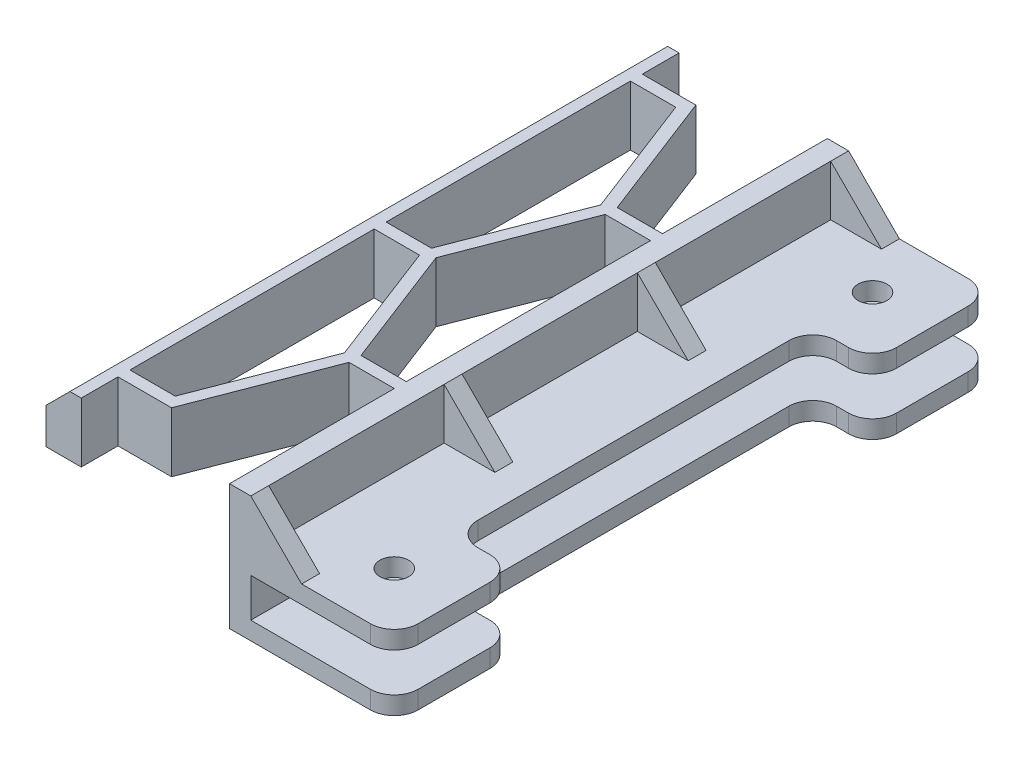
SolidWorks part; units mm, degrees
ref_plane "Front Plane" through (0, 0, 0) normal (0, 0, 1) x (1, 0, 0)
ref_plane "Top Plane" through (0, 0, 0) normal (0, 1, 0) x (1, 0, 0)
ref_plane "Right Plane" through (0, 0, 0) normal (1, 0, 0) x (0, 0, -1)
ref_plane "Plane1" through (0, 4, 0) normal (0, 1, 0) x (1, 0, 0)
ref_plane "Plane2" through (0, 3.25, 0) normal (0, 1, 0) x (1, 0, 0)
sketch "Sketch1" plane through (0, 4, 0) normal (0, 1, 0) x (1, 0, 0)
  line L0 (-14.18, 50) -> (-14.18, 46.9286)
  line L1 (-17.13, 50) -> (-14.18, 50)
  line L2 (-17.13, 50) -> (-17.13, 0)
  line L3 (-17.13, 0) -> (-14.18, 0)
  line L5 (-1.78, 50) -> (0, 50)
  line L7 (-1.78, 0) -> (0, 0)
  line L8 (0, 50) -> (0, 0)
  line L9 (-1.78, 50) -> (-1.78, 36.2143)
  line L18 (-14.18, 25) -> (-1.78, 25) construction
  line L20 (-14.18, 25) -> (-10.0467, 25) construction
  line L21 (-10.0467, 25) -> (-5.9133, 35.7143) construction
  line L22 (-5.9133, 35.7143) -> (-1.78, 35.7143) construction
  line L23 (-5.9133, 35.7143) -> (-10.0467, 46.4286) construction
  line L24 (-10.0467, 46.4286) -> (-14.18, 46.4286) construction
  line L25 (-10.0467, 3.5714) -> (-14.18, 3.5714) construction
  line L26 (-5.9133, 14.2857) -> (-10.0467, 3.5714) construction
  line L27 (-5.9133, 14.2857) -> (-1.78, 14.2857) construction
  line L28 (-10.0467, 25) -> (-5.9133, 14.2857) construction
  line L29 (-6.4492, 35.7143) -> (-10.3897, 45.9286)
  line L30 (-10.3897, 45.9286) -> (-14.18, 45.9286)
  line L31 (-5.5703, 36.2143) -> (-1.78, 36.2143)
  line L32 (-10.3897, 25.5) -> (-6.4492, 35.7143)
  line L33 (-14.18, 25.5) -> (-10.3897, 25.5)
  line L34 (-9.5108, 25) -> (-5.5703, 14.7857)
  line L35 (-5.5703, 14.7857) -> (-1.78, 14.7857)
  line L36 (-5.5703, 13.7857) -> (-9.7036, 3.0714)
  line L37 (-9.7036, 3.0714) -> (-14.18, 3.0714)
  line L38 (-5.5703, 36.2143) -> (-9.7036, 46.9286)
  line L39 (-9.7036, 46.9286) -> (-14.18, 46.9286)
  line L40 (-5.5703, 35.2143) -> (-1.78, 35.2143)
  line L41 (-9.5802, 24.82) -> (-5.5703, 35.2143)
  line L42 (-14.18, 24.5) -> (-10.3897, 24.5)
  line L43 (-10.3897, 24.5) -> (-6.4492, 14.2857)
  line L44 (-5.5703, 13.7857) -> (-1.78, 13.7857)
  line L45 (-6.4492, 14.2857) -> (-10.3897, 4.0714)
  line L46 (-10.3897, 4.0714) -> (-14.18, 4.0714)
  line L47 (-14.18, 45.9286) -> (-14.18, 25.5)
  line L48 (-14.18, 24.5) -> (-14.18, 4.0714)
  line L49 (-14.18, 3.0714) -> (-14.18, 0)
  line L50 (-1.78, 35.2143) -> (-1.78, 14.7857)
  line L51 (-1.78, 13.7857) -> (-1.78, 0)
  line L52 (-10.3897, 25.5) -> (-10.0467, 25.5) construction
  line L53 (-5.9133, 36.2143) -> (-5.5703, 36.2143) construction
  line L54 (-5.9133, 36.2143) -> (-1.78, 36.2143) construction
  line L55 (-5.4468, 35.8942) -> (-5.5703, 36.2143) construction
  line L56 (-5.4468, 35.8942) -> (-9.7036, 46.9286) construction
  line L57 (-5.5703, 35.2143) -> (-5.4468, 35.5343) construction
  line L58 (-9.5802, 24.82) -> (-5.4468, 35.5343) construction
  line L59 (-5.9133, 35.2143) -> (-5.5703, 35.2143) construction
  line L60 (-5.9133, 35.2143) -> (-1.78, 35.2143) construction
  line L61 (-6.3798, 35.5343) -> (-6.4492, 35.7143) construction
  line L62 (-6.3798, 35.5343) -> (-10.3897, 45.9286) construction
  line L63 (-6.4492, 35.7143) -> (-6.3798, 35.8942) construction
  line L64 (-10.5132, 25.18) -> (-6.3798, 35.8942) construction
  line L65 (-9.5802, 25.18) -> (-9.5108, 25) construction
  line L66 (-9.5802, 25.18) -> (-5.4468, 14.4657) construction
  line L67 (-14.18, 25.5) -> (-10.0467, 25.5) construction
  line L68 (-10.5132, 25.18) -> (-10.3897, 25.5) construction
  line L69 (-10.5132, 24.82) -> (-10.3897, 24.5) construction
  line L70 (-10.5132, 24.82) -> (-6.3798, 14.1058) construction
  line L71 (-10.3897, 24.5) -> (-10.0467, 24.5) construction
  line L72 (-14.18, 24.5) -> (-10.0467, 24.5) construction
  line L73 (-5.9133, 14.7857) -> (-5.5703, 14.7857) construction
  line L74 (-5.9133, 14.7857) -> (-1.78, 14.7857) construction
  line L75 (-5.5703, 14.7857) -> (-5.4468, 14.4657) construction
  line L76 (-5.4468, 14.1058) -> (-5.5703, 13.7857) construction
  line L77 (-5.4468, 14.1058) -> (-9.7036, 3.0714) construction
  line L78 (-5.9133, 13.7857) -> (-5.5703, 13.7857) construction
  line L79 (-5.9133, 13.7857) -> (-1.78, 13.7857) construction
  line L80 (-6.4492, 14.2857) -> (-6.3798, 14.1058) construction
  line L81 (-6.3798, 14.4657) -> (-6.4492, 14.2857) construction
  line L82 (-6.3798, 14.4657) -> (-10.3897, 4.0714) construction
  dimension "D2" = 12.4
  dimension "D4" = 4.1333
  dimension "D5" = 4.1333
  dimension "D7" = 14.2857
  dimension "D1" = 50
  dimension "D3" = 2.95
  dimension "D10" = 25
  dimension "D11" = 25
  dimension "D6" = 1.78
  dimension "D8" = 0.5
  dimension "D9" = 0.5
extrude "Boss-Extrude1" add sketch "Sketch1" along normal blind 5 contours L44 L51 L7 L8 L5 L9 L31 L38 L39 L0 L1 L2 L3 L49 L37 L36 L40 L50 L35 L34 L41 L47 L30 L29 L32 L33 L48 L42 L43 L45 L46 region at (-9.6996, 4, -25)
sketch "Sketch5" plane through (0, 0, 0) normal (0, -1, 0) x (1, 0, 0)
  line L0 (12, -40) -> (12, -50)
  line L1 (0, 0) -> (12, 0)
  line L2 (0, 0) -> (0, -50)
  line L3 (0, -50) -> (12, -50)
  line L4 (12, 0) -> (12, -10)
  line L5 (12, -10) -> (7, -10)
  line L7 (12, -40) -> (7, -40)
  line L8 (7, -10) -> (7, -40)
  line L9 (0, 0) -> (-1.78, 0)
  line L10 (-1.78, 0) -> (-1.78, -50)
  line L11 (-1.78, -50) -> (0, -50)
  circle A0 centre (7, -5) radius 1.1 construction
  circle A1 centre (7, -45) radius 1.1 construction
  point P9 (7, -25)
  point P10 (0, -25)
  point P17 (12, -5)
  point P19 (12, -45)
  dimension "D4" = 2.2
  dimension "D1" = 30
  dimension "D2" = 12
  dimension "D3" = 5
extrude "Boss-Extrude3" add sketch "Sketch5" along normal blind 1.5 contours L5 L8 L7 L0 L3 L2 L1 L4 | L11 L10 L9 L2 region at (4.8333, 0, -25) region at (-0.89, 0, -25)
extrude "Boss-Extrude4" add sketch "Sketch5<3>" against normal up to next contours L11 L10 L9 L2 region at (-0.89, 0, -25)
sketch "Sketch5<3>" plane through (0, 0, 0) normal (0, -1, 0) x (1, 0, 0) same geometry as "Sketch5"
sketch "Sketch7" plane through (0, 3.25, 0) normal (0, 1, 0) x (1, 0, 0)
  line L8 (12, 40) -> (12, 50)
  line L9 (12, 50) -> (0, 50)
  line L10 (0, 50) -> (0, 0)
  line L11 (0, 0) -> (12, 0)
  line L12 (12, 0) -> (12, 10)
  line L13 (12, 10) -> (7, 10)
  line L14 (7, 10) -> (7, 40)
  line L15 (7, 40) -> (12, 40)
  line L16 (12, 40) -> (12, 50)
  line L17 (12, 50) -> (0, 50)
  line L18 (0, 50) -> (0, 0)
  line L19 (0, 0) -> (12, 0)
  line L20 (12, 0) -> (12, 10)
  line L21 (12, 10) -> (7, 10)
  line L22 (7, 10) -> (7, 40)
  line L23 (7, 40) -> (12, 40)
  dimension "D1" = 0
extrude "Boss-Extrude5" add sketch "Sketch7" along normal blind 1.5
fillet "Fillet1" radius 2 12 edges at (12, -0.75, -10) (7, -0.75, -10) (7, -0.75, -40) (12, -0.75, -40) (12, -0.75, -50) (12, -0.75, 0) (12, 4, -50) (12, 4, -40) (7, 4, -40) (7, 4, -10) (12, 4, -10) (12, 4, 0)
sketch "Sketch8" plane through (0, -1.5, 0) normal (0, -1, 0) x (1, 0, 0)
  line L0 (12, -2) -> (12, -8) construction
  line L1 (12, -42) -> (12, -48) construction
  circle A0 centre (7, -5) radius 1.1 construction
  circle A1 centre (7, -45) radius 1.1 construction
  point P6 (0, 0)
  point P7 (7, -44.7374)
  point P8 (7, -5.7763)
  point P9 (0, 0)
  point P10 (12, -5)
  point P13 (12, -45)
  dimension "D1" = 2.2
  dimension "D2" = 5
hole_wizard "CSK for M2 Flat Head Machine Screw2" positions "Sketch9" profile "Sketch10" countersink size "M2" standard "ANSI Metric" end condition through all
sketch "Sketch9" plane through (0, -1.5, 0) normal (0, -1, 0) x (-1, 0, 0)
  point P0 (-7, 45)
  point P3 (-7, 5)
sketch "Sketch10" plane through (7, -1.5, -45) normal (1, 0, 0) x (0, 0, -1)
  line L0 (0, 0) -> (0, 10.5)
  line L1 (0, 10.5) -> (1.2, 10.5)
  line L2 (1.2, 10.5) -> (1.2, 1)
  line L3 (1.2, 1) -> (2.2, 0)
  line L5 (2.2, 0) -> (0, 0)
  line L6 (-1.2, 1) -> (-2.2, 0) construction
  line L11 (0, -6.35) -> (0, 107.95) construction
  dimension "Thru Hole Dia." = 2.4
  dimension "Thru Hole Depth" = 10.5
  dimension "Near C'Sink Dia." = 4.4
  dimension "Near C'Sink Angle" = 90
chamfer "Chamfer1" distance 2 angle 45 1 edges at (-17.13, 9, -25)
sketch "Sketch11" plane through (0, 0, 0) normal (0, 0, 1) x (1, 0, 0)
  line L0 (0, 9) -> (0, 4.75)
  line L1 (0, 4.75) -> (4.25, 4.75)
  line L2 (0, 4.75) -> (10, 4.75) construction
  line L3 (4.25, 4.75) -> (0, 9)
  dimension "D1" = 45
extrude "Boss-Extrude6" add sketch "Sketch11" against normal blind 1.5
pattern_linear "LPattern1" count 4 spacing 16.1667 along (0, 0, -1) of "Boss-Extrude6"
equation "\"bracket-length\"= 50"
equation "\"gap\"= 15 - 2.6"
equation "\"D4@Sketch1\"=\"gap\"/3"
equation "\"D5@Sketch1\"=\"gap\"/3"
equation "\"D2@Sketch1\"=\"gap\""
equation "\"D7@Sketch1\"=\"bracket-length\"/3.5"
equation "\"D1@Sketch1\"=\"bracket-length\""
equation "\"D10@Sketch1\"=\"bracket-length\"/2"
